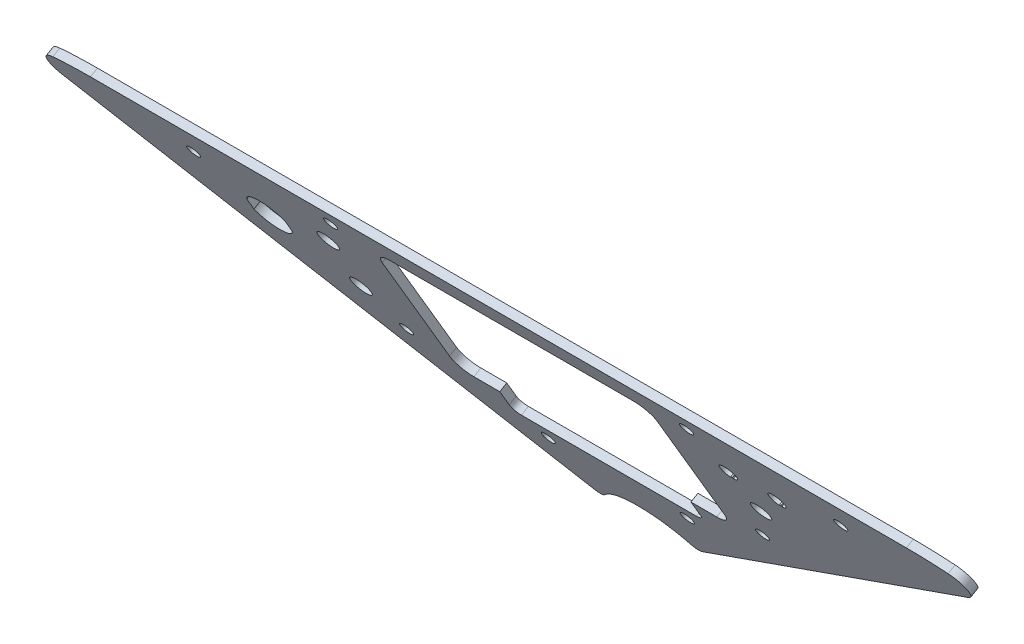
SolidWorks part; units mm, degrees
material "Thornel VCB-20 Carbon Cloth"
ref_plane "Front Plane" through (0, 0, 0) normal (0, 0, 1) x (1, 0, 0)
ref_plane "Top Plane" through (0, 0, 0) normal (0, 1, 0) x (1, 0, 0)
ref_plane "Right Plane" through (0, 0, 0) normal (1, 0, 0) x (0, 0, -1)
ref_plane "Plane1" through (0, -119.0262, 202.5184) normal (0, 0.5067, -0.8621) x (-1, 0, 0)
ref_axis "Axis1" through (-138.1707, 616.7078, 646.8636) along (0.8355, -0.4738, -0.2785)
sketch "Sketch2" plane through (0, -119.0262, 202.5184) normal (0, 0.5067, -0.8621) x (-1, 0, 0)
  line L0 (21.0542, 782.405) -> (177.8755, 885.5596)
  line L1 (138.1707, 859.4424) -> (70.4504, 814.8971) construction
  line L2 (0, 1972.2008) -> (0, -1972.2008) construction
  line L5 (0, 898.6914) -> (0, 768.5559) construction
  line L7 (160.0992, 922.5039) -> (160.0992, 897.1039) construction
  line L9 (160.0992, 898.6914) -> (-160.0992, 898.6914)
  line L10 (-160.0992, 897.1039) -> (160.0992, 897.1039) construction
  line L11 (-21.0542, 782.405) -> (-177.8755, 885.5596)
  arc A0 (16.8957, 782.9949) -> (-16.8957, 782.9949) centre (0, 768.5559) ccw
  circle A3 centre (-127, 884.165) radius 2.4892
  circle A4 centre (-27.2422, 806.1914) radius 2.4892
  circle A5 centre (27.2422, 806.1914) radius 2.4892
  circle A6 centre (127, 884.165) radius 2.4892
  arc A7 (160.0992, 898.6914) -> (175.6846, 897.0805) centre (160.0992, 822.4914) cw
  arc A8 (175.6846, 897.0805) -> (177.8755, 885.5596) centre (174.3858, 890.8648) cw
  arc A9 (-160.0992, 898.6914) -> (-175.6846, 897.0805) centre (-160.0992, 822.4914) ccw
  arc A10 (-175.6846, 897.0805) -> (-177.8755, 885.5596) centre (-174.3858, 890.8648) ccw
  arc A11 (21.0542, 782.405) -> (16.8957, 782.9949) centre (19.3094, 785.0576) cw
  arc A12 (-21.0542, 782.405) -> (-16.8957, 782.9949) centre (-19.3094, 785.0576) ccw
  point P37 (18.5681, 780.7697)
  point P40 (-18.5681, 780.7697)
  dimension "D1" = 22.225
  dimension "D2" = 1.5875
  dimension "D3" = 6.35
  dimension "D4" = 4.9784
  dimension "D5" = 76.2
  dimension "D6" = 3.175
extrude "Boss-Extrude1" add sketch "Sketch2" along normal blind 3.175
sketch "Sketch4" plane through (0, -117.4174, 199.7812) normal (0, 0.5067, -0.8621) x (-1, 0, 0)
  circle A0 centre (-69.85, 890.7539) radius 2.4892
  circle A1 centre (-69.85, 832.0164) radius 2.4892
  circle A2 centre (69.85, 832.0164) radius 2.4892
  circle A3 centre (69.85, 890.7539) radius 2.4892
  dimension "D1" = 4.9784
extrude "Cut-Extrude1" cut sketch "Sketch4" against normal through all
sketch "Sketch6" plane through (0, -119.0262, 202.5184) normal (0, -0.5067, 0.8621) x (1, 0, 0)
  circle A0 centre (-79.654, 873.2914) radius 4
  circle A1 centre (-79.654, 847.8914) radius 4
  dimension "D1" = 8
extrude "Cut-Extrude3" cut sketch "Sketch6" against normal through all
sketch "Sketch5" plane through (0, -117.4174, 199.7812) normal (0, 0.5067, -0.8621) x (-1, 0, 0)
  line L1 (21.0542, 782.405) -> (177.8755, 885.5596) construction
  line L2 (99.2157, 862.57) -> (99.2157, 868.1378)
  line L3 (114.2157, 868.1378) -> (114.2157, 862.57)
  line L5 (160.0992, 898.6914) -> (-160.0992, 898.6914) construction
  arc A0 (99.2157, 862.57) -> (114.2157, 862.57) centre (106.7157, 865.3539) ccw
  arc A1 (114.2157, 868.1378) -> (99.2157, 868.1378) centre (106.7157, 865.3539) ccw
  point P3 (79.654, 873.2914)
  dimension "D1" = 16
  dimension "D3" = 22.225
  dimension "D2" = 33.3375
  dimension "D4" = 15
extrude "Cut-Extrude2" cut sketch "Sketch5" against normal through all
sketch "Sketch7" plane through (0, -117.4174, 199.7812) normal (0, 0.5067, -0.8621) x (-1, 0, 0)
  line L0 (-69.85, 890.7539) -> (-69.85, 832.0164) construction
  line L1 (-80.925, 865.9977) -> (-73.025, 865.9977) construction
  line L2 (-80.925, 865.9977) -> (-80.925, 878.9977) construction
  line L3 (-80.925, 878.9977) -> (-73.025, 878.9977) construction
  line L4 (-73.025, 865.9977) -> (-73.025, 878.9977) construction
  line L5 (-80.925, 865.9977) -> (-73.025, 878.9977) construction
  line L6 (-80.925, 878.9977) -> (-73.025, 865.9977) construction
  line L7 (-92.075, 865.9977) -> (-99.975, 865.9977) construction
  line L8 (-92.075, 865.9977) -> (-92.075, 878.9977) construction
  line L9 (-92.075, 878.9977) -> (-99.975, 878.9977) construction
  line L10 (-99.975, 865.9977) -> (-99.975, 878.9977) construction
  line L11 (-92.075, 865.9977) -> (-99.975, 878.9977) construction
  line L12 (-92.075, 878.9977) -> (-99.975, 865.9977) construction
  line L13 (-96.025, 872.4977) -> (-80.15, 853.4477) construction
  line L15 (-77.2798, 869.2608) -> (-77.2798, 869.9577)
  line L16 (-77.2798, 869.9577) -> (-76.6702, 869.9577)
  line L17 (-76.6702, 869.2608) -> (-76.6702, 869.9577)
  line L19 (-96.3298, 869.2608) -> (-96.3298, 869.9577)
  line L20 (-96.3298, 869.9577) -> (-95.7202, 869.9577)
  line L21 (-95.7202, 869.2608) -> (-95.7202, 869.9577)
  line L22 (-80.15, 853.4477) -> (-76.975, 872.4977) construction
  line L24 (-73.45, 847.1977) -> (-86.85, 847.1977) construction
  line L25 (-73.45, 847.1977) -> (-73.45, 859.6977) construction
  line L26 (-73.45, 859.6977) -> (-86.85, 859.6977) construction
  line L27 (-86.85, 847.1977) -> (-86.85, 859.6977) construction
  line L28 (-73.45, 847.1977) -> (-86.85, 859.6977) construction
  line L29 (-73.45, 859.6977) -> (-86.85, 847.1977) construction
  circle A0 centre (-69.85, 890.7539) radius 2.4892 construction
  arc A1 (-76.6702, 869.2608) -> (-77.2798, 869.2608) centre (-76.975, 872.4977) ccw
  arc A2 (-95.7202, 869.2608) -> (-96.3298, 869.2608) centre (-96.025, 872.4977) ccw
  circle A3 centre (-80.15, 853.4477) radius 3.75
  point P0 (-76.975, 872.4977)
  point P5 (-96.025, 872.4977)
  point P10 (-69.85, 861.3852)
  point P33 (-86.5, 853.7865)
  dimension "D5" = 6.5024
  dimension "D9" = 7.5
  dimension "D1" = 13
  dimension "D2" = 7.9
  dimension "D3" = 19.05
  dimension "D4" = 3.175
  dimension "D6" = 11.1125
  dimension "D7" = 0.6096
  dimension "D8" = 5.7912
  dimension "D10" = 12.5
  dimension "D11" = 13.4
  dimension "D12" = 19.05
  dimension "D13" = 3.175
extrude "Cut-Extrude4" cut sketch "Sketch7" against normal through all
sketch "Sketch8" plane through (0, -117.4174, 199.7812) normal (0, 0.5067, -0.8621) x (-1, 0, 0)
  line L1 (47.65, 888.4289) -> (-47.65, 888.4289)
  line L2 (54, 882.0789) -> (54, 829.9789)
  line L3 (47.65, 823.6289) -> (37.5, 823.6289)
  line L4 (-54, 882.0789) -> (-54, 829.9789)
  line L5 (54, 888.4289) -> (-54, 823.6289) construction
  line L6 (54, 823.6289) -> (-54, 888.4289) construction
  line L7 (-52.4125, 886.8414) -> (-52.4125, 825.2164) construction
  line L8 (52.4125, 825.2164) -> (52.4125, 886.8414) construction
  line L9 (-52.4125, 825.2164) -> (52.4125, 825.2164) construction
  line L10 (52.4125, 886.8414) -> (-52.4125, 886.8414) construction
  line L11 (-37.5, 816.2874) -> (-37.5, 823.6289)
  line L12 (-37.5, 813.1124) -> (-37.5, 817.8749) construction
  line L13 (37.5, 823.6289) -> (37.5, 816.2874)
  line L14 (34.325, 813.1124) -> (-34.325, 813.1124)
  line L15 (-37.5, 823.6289) -> (-47.65, 823.6289)
  arc A0 (-47.65, 823.6289) -> (-54, 829.9789) centre (-47.65, 829.9789) cw
  arc A1 (54, 829.9789) -> (47.65, 823.6289) centre (47.65, 829.9789) cw
  arc A2 (47.65, 888.4289) -> (54, 882.0789) centre (47.65, 882.0789) cw
  arc A3 (-47.65, 888.4289) -> (-54, 882.0789) centre (-47.65, 882.0789) ccw
  arc A4 (37.5, 816.2874) -> (34.325, 813.1124) centre (34.325, 816.2874) cw
  arc A5 (-37.5, 816.2874) -> (-34.325, 813.1124) centre (-34.325, 816.2874) ccw
  point P0 (0, 856.0289)
  point P34 (37.5, 813.1124)
  point P37 (-37.5, 813.1124)
  dimension "D5" = 6.35
  dimension "D6" = 3.175
  dimension "D1" = 1.5875
  dimension "D2" = 1.5875
  dimension "D3" = 1.5875
  dimension "D4" = 1.5875
extrude "Cut-Extrude5" cut sketch "Sketch8" against normal through all
